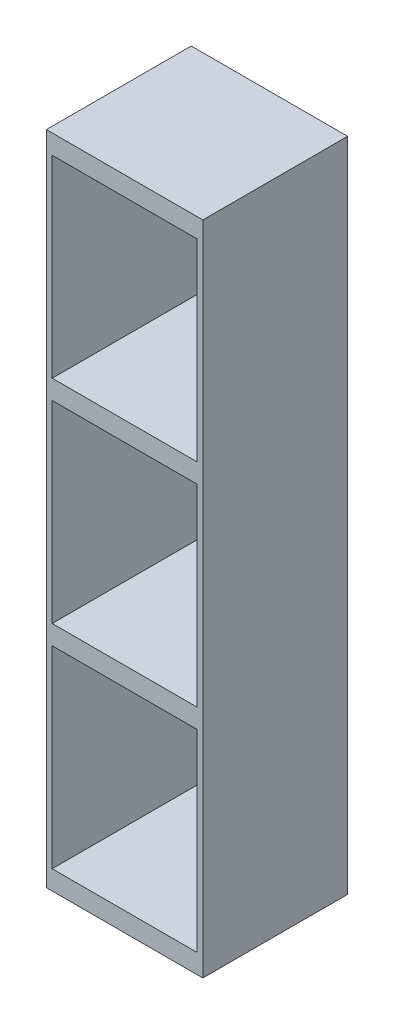
SolidWorks part; units mm, degrees
ref_plane "Front Plane" through (0, 0, 0) normal (0, 0, 1) x (1, 0, 0)
ref_plane "Top Plane" through (0, 0, 0) normal (0, 1, 0) x (1, 0, 0)
ref_plane "Right Plane" through (0, 0, 0) normal (1, 0, 0) x (0, 0, -1)
sketch "Sketch3" plane through (0, 0, 0) normal (0, 1, 0) x (1, 0, 0)
  line L1 (-37.5, -37.5) -> (37.5, -37.5)
  line L2 (-37.5, -37.5) -> (-37.5, 37.5)
  line L3 (-37.5, 37.5) -> (37.5, 37.5)
  line L4 (37.5, -37.5) -> (37.5, 37.5)
  line L5 (-37.5, -37.5) -> (37.5, 37.5) construction
  line L6 (-37.5, 37.5) -> (37.5, -37.5) construction
  line L7 (-37.5, 37.5) -> (-40.5, 37.5)
  line L8 (-37.5, 37.5) -> (-37.5, -37.5)
  line L9 (-37.5, -37.5) -> (-40.5, -37.5)
  line L10 (-40.5, 37.5) -> (-40.5, -37.5)
  line L11 (37.5, 37.5) -> (40.5, 37.5)
  line L12 (37.5, 37.5) -> (37.5, -37.5)
  line L13 (37.5, -37.5) -> (40.5, -37.5)
  line L14 (40.5, 37.5) -> (40.5, -37.5)
  point P0 (0, 0)
  dimension "D1" = 75
  dimension "D2" = 75
  dimension "D3" = 3
  dimension "D4" = 3
extrude "Boss-Extrude2" add sketch "Sketch3" along normal blind 10 contours L1 L4 L3 L2 region at (0, 0, 0)
pattern_linear "LPattern1" count 4 spacing 110 along (0, 1, 0) of bodies 102
extrude "Boss-Extrude5" add sketch "Sketch3<5>" along normal blind 340 contours L14 L11 L4 L13 | L7 L10 L9 L2 region at (-39, 0, 0) region at (39, 0, 0)
sketch "Sketch3<5>" plane through (0, 0, 0) normal (0, 1, 0) x (1, 0, 0) same geometry as "Sketch3"
